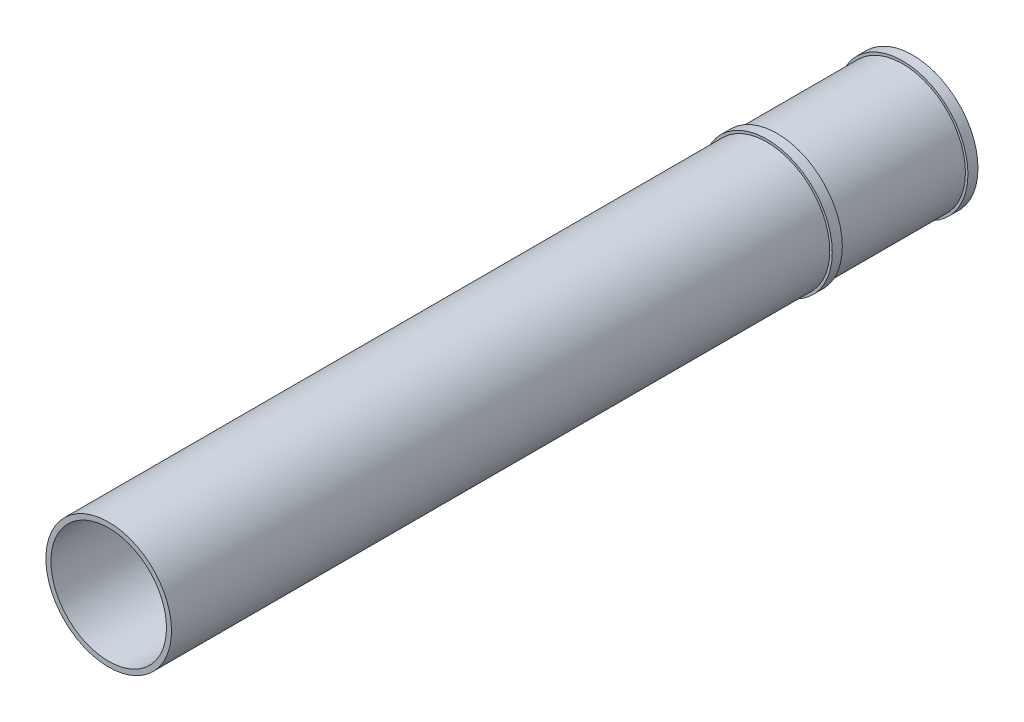
SolidWorks part; units mm, degrees
ref_plane "Front Plane" through (0, 0, 0) normal (0, 0, 1) x (1, 0, 0)
ref_plane "Top Plane" through (0, 0, 0) normal (0, 1, 0) x (1, 0, 0)
ref_plane "Right Plane" through (0, 0, 0) normal (1, 0, 0) x (0, 0, -1)
sketch "Sketch2" plane through (0, 0, 0) normal (0, 0, 1) x (1, 0, 0)
  circle A0 centre (0, 0) radius 25
  circle A1 centre (0, 0) radius 23
  circle A2 centre (0, 0) radius 26
  dimension "D1" = 50
  dimension "D2" = 2
  dimension "D3" = 1
extrude "Boss-Extrude1" add sketch "Sketch2" along normal blind 320 contours A0 A1 region at (-24.2929, 0, 0)
extrude "Boss-Extrude2" add sketch "Sketch2<3>" along normal blind 4 from offset 54 contours A2 A0 region at (-25.2646, 0, 0)
sketch "Sketch2<3>" plane through (0, 0, 0) normal (0, 0, 1) x (1, 0, 0) same geometry as "Sketch2"
extrude "Boss-Extrude3" add sketch "Sketch2<4>" along normal blind 4 contours A2 A0 region at (-25.2646, 0, 0)
sketch "Sketch2<4>" plane through (0, 0, 0) normal (0, 0, 1) x (1, 0, 0) same geometry as "Sketch2"
